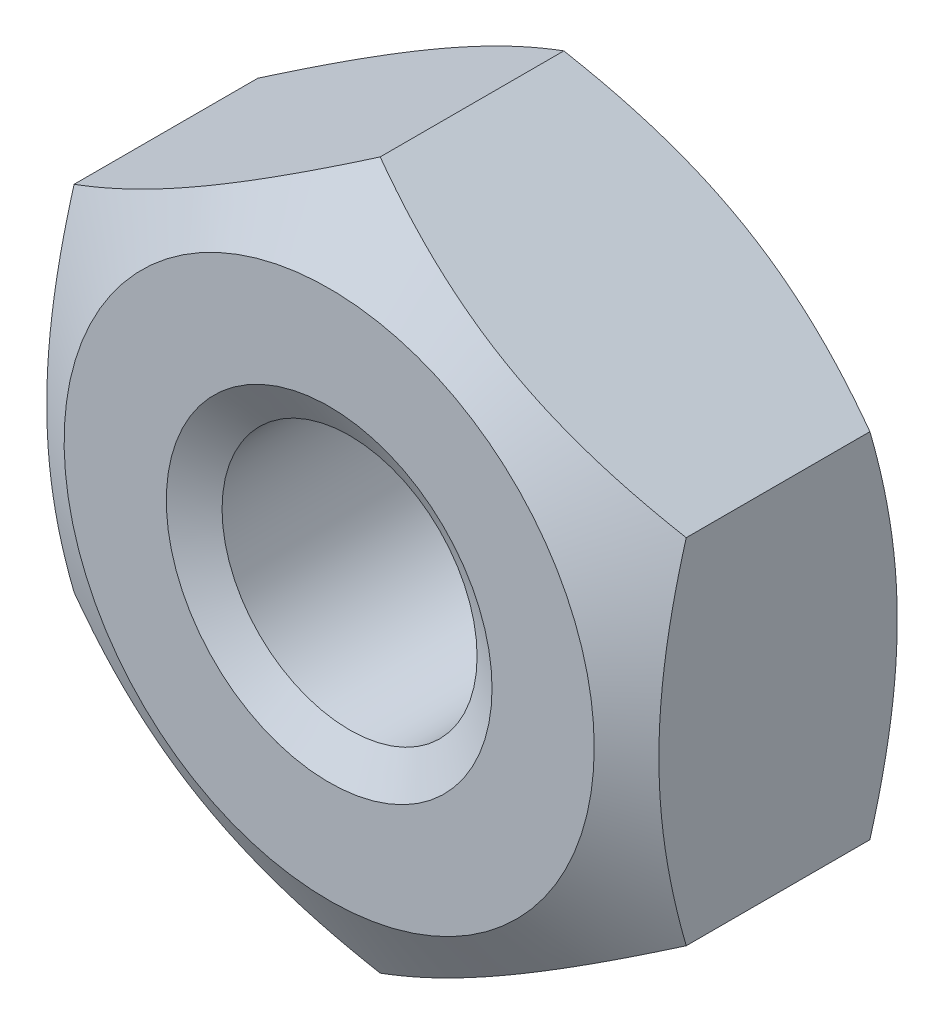
SolidWorks part; units mm, degrees
ref_plane "Front Plane" through (0, 0, 0) normal (0, 0, 1) x (1, 0, 0)
ref_plane "Top Plane" through (0, 0, 0) normal (0, 1, 0) x (1, 0, 0)
ref_plane "Right Plane" through (0, 0, 0) normal (1, 0, 0) x (0, 0, -1)
sketch "Sketch1" plane through (0, 0, 0) normal (0, 0, 1) x (1, 0, 0)
  line L1 (0, 1.7321) -> (-1.5, 0.866)
  line L2 (-1.5, 0.866) -> (-1.5, -0.866)
  line L3 (-1.5, -0.866) -> (0, -1.7321)
  line L4 (0, -1.7321) -> (1.5, -0.866)
  line L5 (1.5, -0.866) -> (1.5, 0.866)
  line L6 (1.5, 0.866) -> (0, 1.7321)
  circle A0 centre (0, 0) radius 1.5 construction
  dimension "D1" = 3
extrude "Boss-Extrude1" add sketch "Sketch1" against normal blind 1.4
sketch "Sketch2" plane through (0, 0, 0) normal (1, 0, 0) x (0, 0, -1)
  line L0 (0, -1.299) -> (0.25, -1.7321)
  line L1 (0, -1.7321) -> (0, -0.866) construction
  line L2 (1.4, -1.7321) -> (0, -1.7321) construction
  line L3 (0.25, -1.7321) -> (0, -1.7321)
  line L4 (0, -1.7321) -> (0, -1.299)
  line L5 (0, 0) -> (1.4, 0) construction
  line L6 (0, -0.866) -> (0, 0.866) construction
  line L7 (1.4, -0.866) -> (1.4, 0.866) construction
  line L8 (0.7, 0) -> (0.7, 1.7321) construction
  line L9 (1.4, 1.7321) -> (0, 1.7321) construction
  line L10 (1.4, -1.7321) -> (1.4, -1.299)
  line L11 (1.15, -1.7321) -> (1.4, -1.7321)
  line L12 (1.4, -1.299) -> (1.15, -1.7321)
  dimension "D1" = 30
revolve "Cut-Revolve1" cut sketch "Sketch2" angle 360 about L5
hole_wizard "M1.7 Tapped Hole1" positions "Sketch4" profile "Sketch3" tap size "M1.6" standard "DIN" end condition through all
sketch "Sketch4" plane through (0, 0, 0) normal (0, 0, 1) x (1, 0, 0)
  point P0 (0, 0)
sketch "Sketch3" plane through (0, 0, 0) normal (1, 0, 0) x (0, -1, 0)
  line L0 (0, 0) -> (0, 1.4)
  line L1 (0, 1.4) -> (0.625, 1.4)
  line L2 (0.625, 1.4) -> (0.625, 0)
  line L5 (0.625, 0) -> (0, 0)
  line L11 (0, -6.35) -> (0, 107.95) construction
  dimension "Thru Tap Drill Dia." = 1.25
  dimension "Thru Tap Drill Depth" = 1.4
cosmetic thread "Hole Thread1" parameters "D2"=1.6
sketch "Sketch5" plane through (0, 0, 0) normal (1, 0, 0) x (0, 0, -1)
  line L2 (0, 0) -> (1.4, 0) construction
  line L3 (1.4, -1.299) -> (1.4, 1.299) construction
chamfer "Chamfer1" distance 0.1 angle 60 1 edges at (0.625, 0, 0) first distance on face at (0.625, 0, -1.4)
